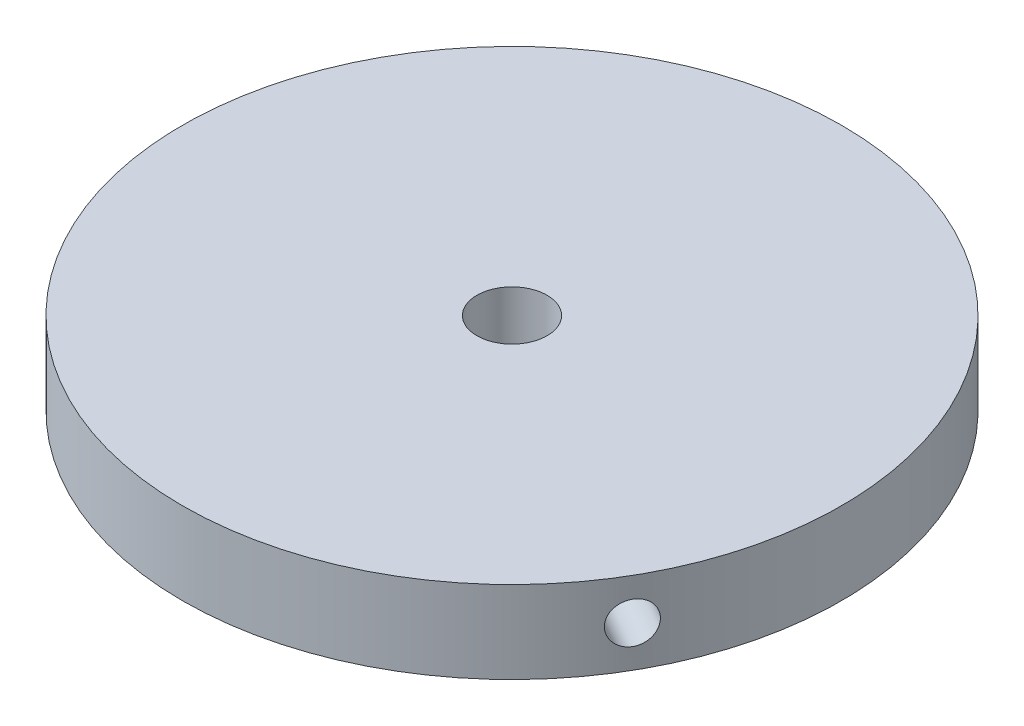
SolidWorks part; units mm, degrees
material "G10 Fiberglass"
ref_plane "Front Plane" through (0, 0, 0) normal (0, 0, 1) x (1, 0, 0)
ref_plane "Top Plane" through (0, 0, 0) normal (0, 1, 0) x (1, 0, 0)
ref_plane "Right Plane" through (0, 0, 0) normal (1, 0, 0) x (0, 0, -1)
sketch "Sketch1" plane through (0, 0, 0) normal (0, 1, 0) x (1, 0, 0)
  circle A0 centre (0, 0) radius 38.1508
  dimension "D1" = 76.3016
extrude "Boss-Extrude1" add sketch "Sketch1" along normal blind 9.525
ref_plane "Plane1" through (-33.0396, 0, 19.0754) normal (-0.866, 0, 0.5) x (0, -1, 0)
sketch "Sketch4" plane through (-33.0396, 0, 19.0754) normal (-0.866, 0, 0.5) x (0, -1, 0)
  circle A0 centre (-4.7625, 0) radius 2.3749
  dimension "D1" = 4.7625
  dimension "D2" = 4.7498
extrude "Cut-Extrude2" cut sketch "Sketch4" against normal blind 6.35
ref_axis "Axis1" through (0, 10.0012, 0) along (0, -1, 0)
pattern_circular "CirPattern1" count 3 over 360 about axis through (0, 10.0012, 0) along (0, -1, 0) of "Cut-Extrude2"
sketch "Sketch6" plane through (0, 9.525, 0) normal (0, 1, 0) x (1, 0, 0)
  circle A0 centre (0, 0) radius 4.064
  dimension "D1" = 8.128
extrude "Cut-Extrude4" cut sketch "Sketch6" against normal through all
